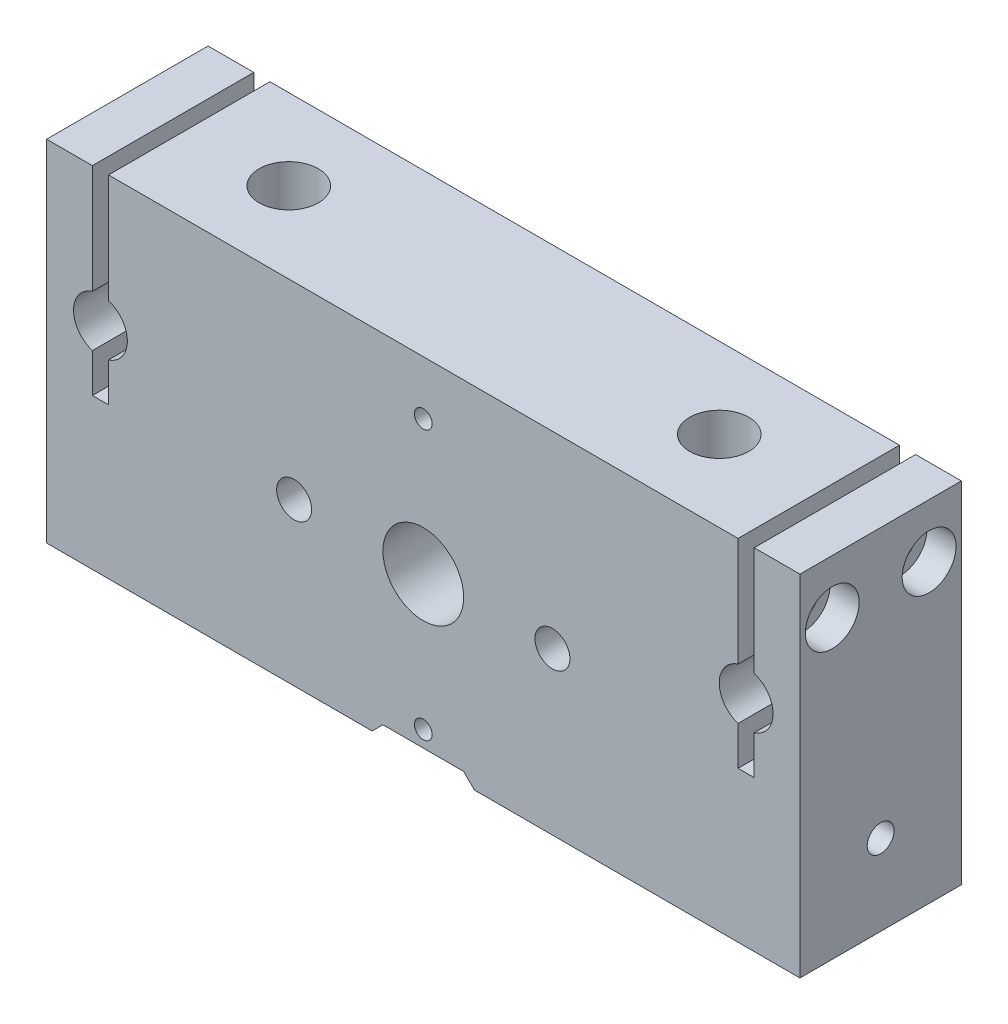
SolidWorks part; units mm, degrees
material "6061 Alloy"
ref_plane "Ön Düzlem" through (0, 0, 0) normal (0, 0, 1) x (1, 0, 0)
ref_plane "Üst Düzlem" through (0, 0, 0) normal (0, 1, 0) x (1, 0, 0)
ref_plane "Sağ Düzlem" through (0, 0, 0) normal (1, 0, 0) x (0, 0, -1)
sketch "Sketch1" plane through (0, 0, 0) normal (0, 0, 1) x (1, 0, 0)
  line L1 (-70, 32.5) -> (70, 32.5)
  line L2 (-70, 32.5) -> (-70, -32.5)
  line L3 (-70, -32.5) -> (70, -32.5)
  line L4 (70, 32.5) -> (70, -32.5)
  line L5 (-70, 32.5) -> (70, -32.5) construction
  line L6 (-70, -32.5) -> (70, 32.5) construction
  point P0 (0, 0)
  dimension "D1" = 65
  dimension "D2" = 140
extrude "Boss-Extrude1" add sketch "Sketch1" along normal blind 30
sketch "Sketch2" plane through (0, 0, 30) normal (0, 0, -1) x (-1, 0, 0)
  line L0 (0, -2.5) -> (0, 32.5) construction
  line L1 (0, -2.5) -> (24, -2.5) construction
  line L2 (-70, 32.5) -> (70, 32.5) construction
  circle A0 centre (0, -2.5) radius 7.5
  circle A1 centre (24, -2.5) radius 3.25
  circle A2 centre (-24, -2.5) radius 3.25
  dimension "D1" = 35
  dimension "D2" = 6.5
  dimension "D4" = 15
  dimension "D3" = 24
extrude "Cut-Extrude2" cut sketch "Sketch2" along normal blind 27
sketch "Sketch4" plane through (0, 0, 3) normal (0, 0, 1) x (1, 0, 0)
  circle A0 centre (0, -2.5) radius 7.5
  dimension "D1" = 15
extrude "Cut-Extrude3" cut sketch "Sketch4" against normal through all
sketch "Sketch5" plane through (0, 0, 0) normal (0, 0, -1) x (-1, 0, 0)
  line L0 (0, -2.5) -> (0, 7.5) construction
  line L1 (-60, 7.5) -> (60, 7.5) construction
  circle A0 centre (-60, 7.5) radius 5
  circle A1 centre (60, 7.5) radius 5
  point P7 (0, 7.5)
  dimension "D3" = 10
  dimension "D1" = 10
  dimension "180" = 120
extrude "Cut-Extrude4" cut sketch "Sketch5" against normal through all
sketch "Sketch6" plane through (0, 0, 0) normal (0, 0, -1) x (-1, 0, 0)
  line L0 (-70, 32.5) -> (70, 32.5) construction
  line L1 (-61.5, 32.5) -> (-58.5, 32.5)
  line L2 (-61.5, 32.5) -> (-61.5, -4.5)
  line L3 (-61.5, -4.5) -> (-58.5, -4.5)
  line L4 (-58.5, 32.5) -> (-58.5, -4.5)
  line L5 (-60, 7.5) -> (-60, 32.5) construction
  line L6 (0, 0) -> (0, 32.5) construction
  line L7 (61.5, -4.5) -> (58.5, -4.5)
  line L8 (58.5, 32.5) -> (58.5, -4.5)
  line L9 (61.5, 32.5) -> (58.5, 32.5)
  line L10 (61.5, 32.5) -> (61.5, -4.5)
  dimension "D1" = 3
  dimension "D2" = 12
extrude "Cut-Extrude5" cut sketch "Sketch6" against normal through all
sketch "Sketch7" plane through (70, 0, 0) normal (1, 0, 0) x (0, 0, -1)
  line L0 (-15, 32.5) -> (-15, 22.5) construction
  line L1 (-30, 32.5) -> (0, 32.5) construction
  line L2 (-24, 22.5) -> (-6, 22.5) construction
  point P7 (-15, 22.5)
  dimension "D1" = 10
  dimension "D2" = 18
hole_wizard "CBORE for M5 Hex Socket Head Cap Screw1" positions "Sketch8" profile "Sketch9" counterbore size "M5" standard "ISO" end condition up to next
sketch "Sketch8" plane through (70, 0, 0) normal (1, 0, 0) x (0, 0, -1)
  point P0 (-6, 22.5)
  point P3 (-24, 22.5)
sketch "Sketch9" plane through (70, 22.5, 6) normal (0, 1, 0) x (0, 0, -1)
  line L0 (0, 0) -> (0, 8.5)
  line L1 (0, 8.5) -> (2.75, 8.5)
  line L3 (2.75, 8.5) -> (2.75, 5.4)
  line L4 (2.75, 5.4) -> (5, 5.4)
  line L5 (5, 5.4) -> (5, 0)
  line L7 (5, 0) -> (0, 0)
  line L11 (0, -6.35) -> (0, 107.95) construction
  dimension "Thru Hole Dia." = 5.5
  dimension "Thru Hole Depth" = 8.5
  dimension "C'Bore Dia." = 10
  dimension "C'Bore Depth" = 5.4
sketch "Sketch10" plane through (58.5, 0, 0) normal (1, 0, 0) x (0, 0, -1)
  point P0 (-24, 22.5)
  point P1 (-6, 22.5)
hole_wizard "Tap Drill for M5 Tap1" positions "Sketch11" profile "Sketch12" hole size "M5" standard "ISO"
sketch "Sketch11" plane through (58.5, 0, 0) normal (1, 0, 0) x (0, 0, -1)
  point P0 (-6, 22.5)
  point P3 (-24, 22.5)
sketch "Sketch12" plane through (58.5, 22.5, 6) normal (0, 1, 0) x (0, 0, -1)
  line L0 (0, 0) -> (0, 13.2618)
  line L1 (0, 13.2618) -> (2.1, 12)
  line L2 (2.1, 12) -> (2.1, 0)
  line L5 (2.1, 0) -> (0, 0)
  line L10 (0, 13.2618) -> (-2.1, 12) construction
  line L11 (0, -6.35) -> (0, 107.95) construction
  dimension "Hole Dia." = 4.2
  dimension "Hole Depth" = 12
  dimension "Drill Angle" = 118
sketch "Sketch13" plane through (70, 0, 0) normal (1, 0, 0) x (0, 0, -1)
  line L0 (-15, -32.5) -> (-15, -17.5) construction
  line L1 (-30, -32.5) -> (0, -32.5) construction
  dimension "D1" = 15
hole_wizard "Tap Drill for M6 Tap1" positions "Sketch14" profile "Sketch15" hole size "M6" standard "ISO"
sketch "Sketch14" plane through (70, 0, 0) normal (1, 0, 0) x (0, 0, -1)
  point P0 (-15, -17.5)
sketch "Sketch15" plane through (70, -17.5, 15) normal (0, 1, 0) x (0, 0, -1)
  line L0 (0, 0) -> (0, 16.5022)
  line L1 (0, 16.5022) -> (2.5, 15)
  line L2 (2.5, 15) -> (2.5, 0)
  line L5 (2.5, 0) -> (0, 0)
  line L10 (0, 16.5022) -> (-2.5, 15) construction
  line L11 (0, -6.35) -> (0, 107.95) construction
  dimension "Hole Dia." = 5
  dimension "Hole Depth" = 15
  dimension "Drill Angle" = 118
mirror "Mirror1" about plane through (0, 0, 0) normal (1, 0, 0) of "Tap Drill for M6 Tap1", "CBORE for M5 Hex Socket Head Cap Screw1", "Tap Drill for M5 Tap1"
sketch "Sketch22" plane through (0, 32.5, 0) normal (0, 1, 0) x (1, 0, 0)
  line L0 (58.5, -15) -> (40, -15) construction
  line L1 (58.5, -30) -> (58.5, 0) construction
  line L2 (40, -15) -> (-40, -15) construction
  line L3 (-40, -15) -> (-58.5, -15) construction
  line L4 (-58.5, -30) -> (-58.5, 0) construction
  dimension "D1" = 80
hole_wizard "CBORE for M6 Hex Socket Head Cap Screw3" positions "Sketch23" profile "Sketch24" counterbore size "M6" standard "ISO" end condition through all
sketch "Sketch23" plane through (0, 32.5, 0) normal (0, 1, 0) x (1, 0, 0)
  point P0 (40, -15)
  point P3 (-40, -15)
sketch "Sketch24" plane through (40, 32.5, 15) normal (1, 0, 0) x (0, 0, 1)
  line L0 (0, 0) -> (0, 65)
  line L1 (0, 65) -> (3.3, 65)
  line L3 (3.3, 65) -> (3.3, 61.4)
  line L4 (3.3, 61.4) -> (5.5, 61.4)
  line L5 (5.5, 61.4) -> (5.5, 0)
  line L7 (5.5, 0) -> (0, 0)
  line L11 (0, -6.35) -> (0, 107.95) construction
  dimension "Thru Hole Dia." = 6.6
  dimension "Thru Hole Depth" = 65
  dimension "C'Bore Dia." = 11
  dimension "C'Bore Depth" = 61.4
sketch "Sketch25" plane through (0, 0, 30) normal (0, 0, 1) x (1, 0, 0)
  line L0 (0, -2.5) -> (0, 22.5) construction
  dimension "D1" = 25
hole_wizard "Tap Drill for M4 Tap1" positions "Sketch26" profile "Sketch28" hole size "M4" standard "ISO"
sketch "Sketch26" plane through (0, 0, 30) normal (0, 0, 1) x (1, 0, 0)
  point P0 (0, 22.5)
sketch "Sketch28" plane through (0, 22.5, 30) normal (1, 0, 0) x (0, -1, 0)
  line L0 (0, 0) -> (0, 8.9914)
  line L1 (0, 8.9914) -> (1.65, 8)
  line L2 (1.65, 8) -> (1.65, 0)
  line L5 (1.65, 0) -> (0, 0)
  line L10 (0, 8.9914) -> (-1.65, 8) construction
  line L11 (0, -6.35) -> (0, 107.95) construction
  dimension "Hole Dia." = 3.3
  dimension "Hole Depth" = 8
  dimension "Drill Angle" = 118
pattern_circular "CirPattern1" count 4 over 360 about axis through (0, -2.5, 3) along (0, 0, 1) skipping 1, 3 of "Tap Drill for M4 Tap1" reverse direction yes
sketch "Sketch29" plane through (0, 0, 30) normal (0, 0, 1) x (1, 0, 0)
  line L0 (-70, -32.5) -> (70, -32.5) construction
  line L2 (-17.5, -30.5) -> (17.5, -30.5)
  line L3 (-17.5, -30.5) -> (-17.5, -32.5)
  line L4 (-17.5, -32.5) -> (17.5, -32.5)
  line L5 (17.5, -30.5) -> (17.5, -32.5)
  point P0 (0, -32.5)
  dimension "D1" = 2
  dimension "D2" = 35
extrude "Cut-Extrude6" cut sketch "Sketch29" against normal through all
chamfer "Chamfer2" distance 10 angle 45 2 edges at (-17.5, -30.5, 15) (17.5, -30.5, 15)
extrude "Cut-Extrude7" cut sketch "Sketch2<2>" along normal through all
sketch "Sketch2<2>" plane through (0, 0, 30) normal (0, 0, -1) x (-1, 0, 0) same geometry as "Sketch2"
